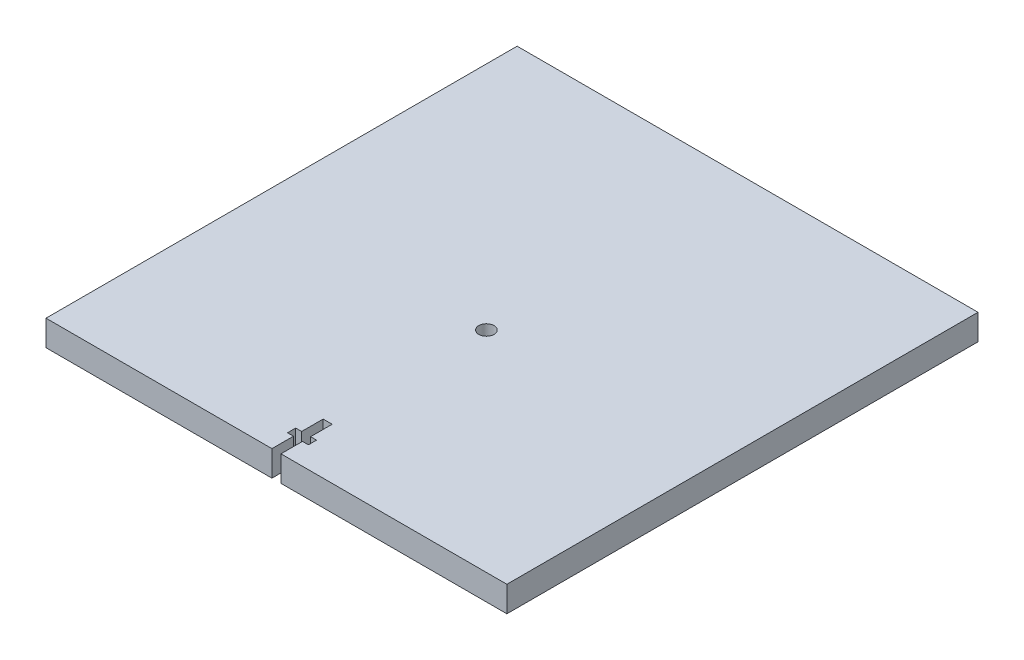
SolidWorks part; units mm, degrees
ref_plane "Front Plane" through (0, 0, 0) normal (0, 0, 1) x (1, 0, 0)
ref_plane "Top Plane" through (0, 0, 0) normal (0, 1, 0) x (1, 0, 0)
ref_plane "Right Plane" through (0, 0, 0) normal (1, 0, 0) x (0, 0, -1)
sketch "Sketch1" plane through (0, 0, 0) normal (0, 1, 0) x (1, 0, 0)
  line L1 (0, 0) -> (142.875, 0)
  line L2 (0, 0) -> (0, 146.05)
  line L3 (0, 146.05) -> (142.875, 146.05)
  line L4 (142.875, 0) -> (142.875, 146.05)
  dimension "D1" = 142.875
  dimension "D2" = 146.05
extrude "Boss-Extrude1" add sketch "Sketch1" along normal blind 7.9375
sketch "Sketch7" plane through (0, 0, 0) normal (-1, 0, 0) x (0, 0, 1)
  line L0 (-146.05, 0) -> (0, 0) construction
  line L1 (-6.35, 0) -> (-95.25, 0)
  line L2 (-6.35, 0) -> (-6.35, 7.9375)
  line L3 (-6.35, 7.9375) -> (-95.25, 7.9375)
  line L4 (-95.25, 0) -> (-95.25, 7.9375)
  line L6 (0, 7.9375) -> (0, 0) construction
  point P10 (0, 0)
  dimension "D1" = 6.35
  dimension "D2" = 7.9375
  dimension "D3" = 88.9
extrude "Boss-Extrude4" [suppressed] add sketch "Sketch7" along normal blind 4.7625
sketch "Sketch8" [suppressed] plane through (142.875, 0, 0) normal (1, 0, 0) x (0, 0, -1)
  line L0 (0, 7.9375) -> (146.05, 7.9375) construction
  line L1 (95.25, 0) -> (12.7, 0)
  line L2 (95.25, 0) -> (95.25, 7.9375)
  line L3 (95.25, 7.9375) -> (12.7, 7.9375)
  line L4 (12.7, 0) -> (12.7, 7.9375)
  line L5 (0, 7.9375) -> (0, 0) construction
  dimension "D1" = 12.7
extrude "Boss-Extrude5" [suppressed] add sketch "Sketch8" along normal blind 4.7625
sketch "Sketch10" plane through (0, 7.9375, 0) normal (0, 1, 0) x (1, 0, 0)
  line L0 (71.4375, 146.05) -> (71.4375, 15.875) construction
  line L1 (70.0405, 9.2075) -> (68.199, 9.2075)
  line L3 (142.875, 146.05) -> (0, 146.05) construction
  line L4 (0, 0) -> (142.875, 0) construction
  line L5 (70.0405, 6.6675) -> (70.0405, 0)
  line L6 (70.0405, 15.875) -> (72.8345, 15.875)
  line L7 (70.0405, 15.875) -> (70.0405, 9.2075)
  line L8 (70.0405, 0) -> (72.8345, 0)
  line L9 (72.8345, 15.875) -> (72.8345, 9.2075)
  line L12 (74.676, 6.6675) -> (72.8345, 6.6675)
  line L13 (74.676, 6.6675) -> (74.676, 9.2075)
  line L14 (74.676, 9.2075) -> (72.8345, 9.2075)
  line L15 (68.199, 6.6675) -> (68.199, 9.2075)
  line L18 (70.0405, 6.6675) -> (68.199, 6.6675)
  line L26 (72.8345, 6.6675) -> (72.8345, 0)
  point P6 (71.4375, 7.9375)
  point P11 (71.4375, 7.9375)
  dimension "D1" = 2.794
  dimension "D2" = 15.875
  dimension "D3" = 2.54
  dimension "D4" = 6.477
extrude "Cut-Extrude2" cut sketch "Sketch10" against normal through all
hole_wizard "3/16 (0.1875) Diameter Hole1" positions "Sketch11" profile "Sketch13" hole size "3/16" standard "ANSI Inch" end condition through all
sketch "Sketch11" plane through (0, 0, 0) normal (0, -1, 0) x (-1, 0, 0)
  line L0 (-142.875, -6.35) -> (0, 136.525) construction
  line L1 (0, 146.05) -> (0, 0) construction
  point P7 (-71.4375, 65.0875)
sketch "Sketch13" plane through (71.4375, 0, -65.0875) normal (1, 0, 0) x (0, 0, -1)
  line L0 (0, 0) -> (0, 7.9375)
  line L1 (0, 7.9375) -> (2.3812, 7.9375)
  line L2 (2.3812, 7.9375) -> (2.3812, 0)
  line L5 (2.3812, 0) -> (0, 0)
  line L11 (0, -6.35) -> (0, 107.95) construction
  dimension "Thru Hole Dia." = 4.7625
  dimension "Thru Hole Depth" = 7.9375
